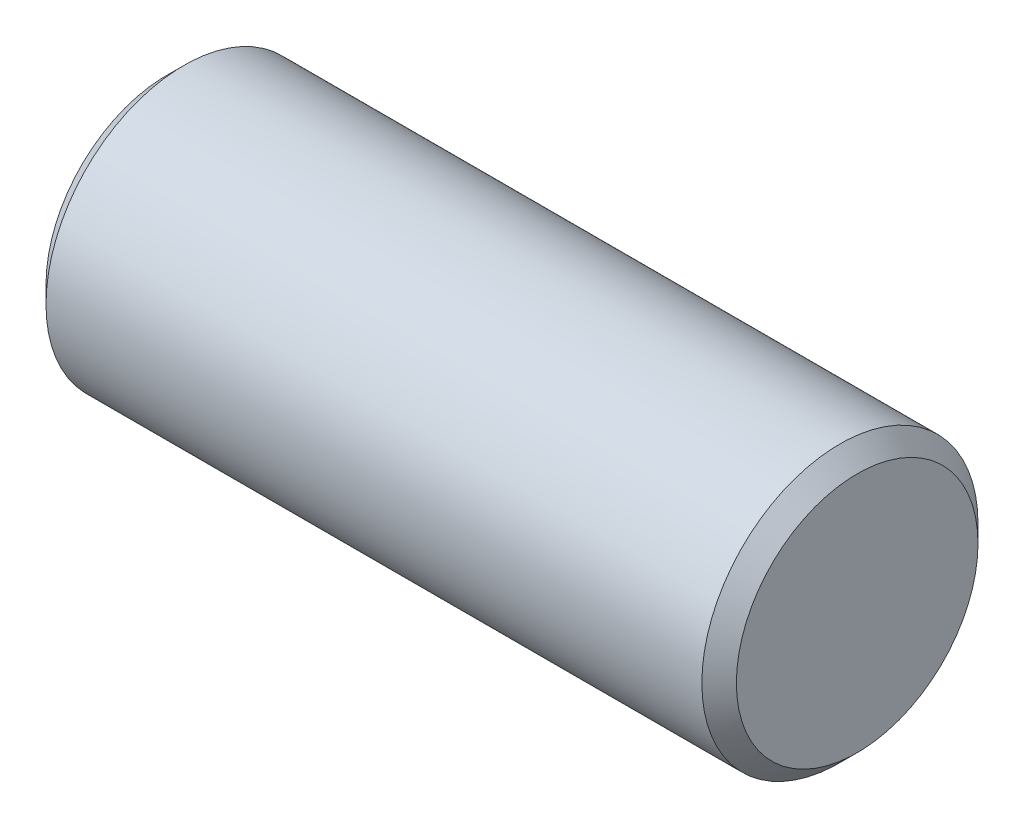
SolidWorks part; units mm, degrees
ref_plane "Front Plane" through (0, 0, 0) normal (0, 0, 1) x (1, 0, 0)
ref_plane "Top Plane" through (0, 0, 0) normal (0, 1, 0) x (1, 0, 0)
ref_plane "Right Plane" through (0, 0, 0) normal (1, 0, 0) x (0, 0, -1)
sketch "Sketch1" plane through (0, 0, 0) normal (0, 0, 1) x (1, 0, 0)
  line L0 (0, 0) -> (20, 0) construction
  line L1 (0, 0) -> (20, 0)
  line L2 (20, 0) -> (20, 4)
  line L3 (20, 4) -> (0, 4)
  line L4 (0, 4) -> (0, 0)
  dimension "L" = 20
  dimension "D" = 8
revolve "Revolve1" add sketch "Sketch1" angle 360 about L0
chamfer "Chamfer1" distance 0.5 angle 45 2 edges at (20, 0, 4) (0, 0, 4)
ref_plane "Plane1" through (0, 0, 4) normal (0, 0, 1) x (1, 0, 0)
ref_plane "Plane2" through (20, 0, 0) normal (1, 0, 0) x (0, 0, -1)
other "DeleteFace1" [suppressed]
chamfer "Chamfer2" [suppressed] distance 2 angle 45
ref_plane "Dim. KC" [suppressed] through (2, 0, 0) normal (1, 0, 0) x (0, 0, -1)
ref_plane "Plane3" [suppressed] through (2, 0, 0) normal (1, 0, 0) x (0, 0, -1)
ref_plane "Plane4" [suppressed] through (8, 0, 0) normal (1, 0, 0) x (0, 0, -1)
sketch "Sketch2" [suppressed] plane through (0, 0, 4) normal (0, 0, 1) x (1, 0, 0)
  line L0 (2, 0) -> (8, 0) construction
  line L1 (2, 1.5) -> (8, 1.5)
  line L2 (2, 1.5) -> (2, -1.5) construction
  line L3 (2, -1.5) -> (8, -1.5)
  line L4 (8, 1.5) -> (8, -1.5) construction
  line L5 (5, 1.5) -> (5, -1.5) construction
  line L6 (2, -4.4) -> (2, 4.4) construction
  line L7 (8, 1.5) -> (8, -1.5)
  line L8 (8, -4.4) -> (8, 4.4) construction
  line L9 (2, 1.5) -> (2, -1.5)
  line L12 (2, -4.4) -> (2, 4.4) construction
  dimension "A" = 6
  dimension "B_s" = 3
extrude "Boss-Extrude1" [suppressed] add sketch "Sketch2" against normal blind 1.8 separate body
fillet "Fillet1" [suppressed] type full round
fillet "Fillet2" [suppressed] type full round
sketch "Sketch3" [suppressed] plane through (0, 0, 4) normal (0, 0, 1) x (1, 0, 0)
  line L0 (9, 1.5) -> (9, -1.5) construction
  line L1 (6.5, 1.5) -> (11.5, 1.5)
  line L2 (6.5, 1.5) -> (6.5, -1.5)
  line L3 (6.5, -1.5) -> (11.5, -1.5)
  line L4 (11.5, 1.5) -> (11.5, -1.5)
  line L7 (6.5, 0) -> (11.5, 0) construction
  line L9 (10, 1.5) -> (10, -1.5) construction
  line L10 (8, 1.5) -> (8, -1.5) construction
  line L11 (2, 1.5) -> (8, 1.5) construction
  line L12 (2, -1.5) -> (8, -1.5) construction
  dimension "D1" = 1.5
  dimension "D2" = 2
  dimension "D3" = 1.5
extrude "Boss-Extrude2" [suppressed] add sketch "Sketch3" against normal blind 1.8
fillet "Fillet3" [suppressed] radius 0.1
other "DeleteFace2" [suppressed]
other "DeleteFace3" [suppressed]
combine bodies "Combine1" [suppressed] operation type subtract main body 101 bodies to subtract 146
ref_plane "KC_SEC1" [suppressed] through (5, 0, 0) normal (1, 0, 0) x (0, 0, -1)
ref_plane "KC_SEC2" [suppressed] through (9, 0, 0) normal (1, 0, 0) x (0, 0, -1)
ref_plane "Dim. WKC" [suppressed] through (2, 0, 0) normal (1, 0, 0) x (0, 0, -1)
ref_plane "Dim. K" [suppressed] through (20, 0, 0) normal (1, 0, 0) x (0, 0, -1)
ref_plane "Plane5" [suppressed] through (2, 0, 0) normal (1, 0, 0) x (0, 0, -1)
ref_plane "Plane6" [suppressed] through (20, 0, 0) normal (1, 0, 0) x (0, 0, -1)
sketch "Sketch4" [suppressed] plane through (0, 0, 4) normal (0, 0, 1) x (1, 0, 0)
  line L0 (2, 1.5) -> (2, -1.5)
  line L1 (2, 1.5) -> (8, 1.5)
  line L2 (2, 1.5) -> (2, -1.5) construction
  line L3 (2, -1.5) -> (8, -1.5)
  line L4 (8, 1.5) -> (8, -1.5)
  line L5 (2, -4.4) -> (2, 4.4) construction
  line L6 (2, -3.3) -> (2, 3.3) construction
  line L7 (8, 0) -> (2, 0) construction
  line L8 (5, 1.5) -> (5, -1.5) construction
  dimension "C" = 6
  dimension "B_s" = 3
extrude "Boss-Extrude3" [suppressed] add sketch "Sketch4" against normal blind 1.8 separate body
sketch "Sketch5" [suppressed] plane through (0, 0, 4) normal (0, 0, 1) x (1, 0, 0)
  line L0 (0, 0) -> (20, 0) construction
  line L2 (20, -3.3) -> (20, 3.3) construction
  line L4 (20, -3.3) -> (20, 3.3) construction
  line L5 (17, 1.5) -> (17, -1.5) construction
  line L9 (14, 1.5) -> (20, 1.5)
  line L10 (14, 1.5) -> (14, -1.5)
  line L11 (14, -1.5) -> (20, -1.5)
  line L12 (20, 1.5) -> (20, -1.5) construction
  line L13 (20, 1.5) -> (20, -1.5)
  dimension "B_s" = 3
  dimension "E" = 6
extrude "Boss-Extrude4" [suppressed] add sketch "Sketch5" against normal blind 1.8 separate body
sketch "Sketch6" [suppressed] plane through (0, 0, 4) normal (0, 0, 1) x (1, 0, 0)
  line L0 (2, 1.5) -> (8, 1.5) construction
  line L1 (6.5, 1.5) -> (11.5, 1.5)
  line L2 (6.5, 1.5) -> (6.5, -1.5)
  line L3 (6.5, -1.5) -> (11.5, -1.5)
  line L4 (11.5, 1.5) -> (11.5, -1.5)
  line L5 (2, -1.5) -> (8, -1.5) construction
  line L6 (8, 1.5) -> (8, -1.5) construction
  line L7 (9, 1.5) -> (9, -1.5) construction
  line L8 (10, 1.5) -> (10, -1.5) construction
  dimension "D1" = 1.5
  dimension "D2" = 2
  dimension "D3" = 1.5
extrude "Boss-Extrude5" [suppressed] add sketch "Sketch6" against normal blind 1.8
fillet "Fillet4" [suppressed] type full round
fillet "Fillet5" [suppressed] type full round
fillet "Fillet6" [suppressed] radius 0.1
fillet "Fillet7" [suppressed] type full round
fillet "Fillet8" [suppressed] type full round
fillet "Fillet9" [suppressed] radius 0.1
other "DeleteFace4" [suppressed]
other "DeleteFace5" [suppressed]
other "DeleteFace6" [suppressed]
other "DeleteFace7" [suppressed]
combine bodies "Combine2" [suppressed] operation type subtract main body 101 bodies to subtract 149 135
ref_plane "WKC_SEC1" [suppressed] through (5, 0, 0) normal (1, 0, 0) x (0, 0, -1)
ref_plane "WKC_SEC2" [suppressed] through (17, 0, 0) normal (1, 0, 0) x (0, 0, -1)
ref_plane "WKC_SEC3" [suppressed] through (9, 0, 0) normal (1, 0, 0) x (0, 0, -1)
ref_plane "Dim. KZ" [suppressed] through (2, 0, 0) normal (1, 0, 0) x (0, 0, -1)
ref_plane "Plane7" [suppressed] through (2, 0, 0) normal (1, 0, 0) x (0, 0, -1)
ref_plane "Plane8" [suppressed] through (8, 0, 0) normal (1, 0, 0) x (0, 0, -1)
sketch "Sketch7" [suppressed] plane through (0, 0, 4) normal (0, 0, 1) x (1, 0, 0)
  line L0 (0, 0) -> (8, 0) construction
  line L1 (2, 1.5) -> (8, 1.5)
  line L2 (2, 1.5) -> (2, -1.5) construction
  line L3 (2, -1.5) -> (8, -1.5)
  line L4 (8, 1.5) -> (8, -1.5) construction
  line L5 (2, -4.4) -> (2, 4.4) construction
  line L6 (2, -4.4) -> (2, 4.4) construction
  line L7 (2, 1.5) -> (2, -1.5)
  line L8 (8, 1.5) -> (8, -1.5)
  line L9 (8, -4.4) -> (8, 4.4) construction
  line L10 (5, 1.5) -> (5, -1.5) construction
  dimension "B_s" = 3
  dimension "Z" = 6
extrude "Boss-Extrude6" [suppressed] add sketch "Sketch7" against normal blind 1.8 separate body
fillet "Fillet10" [suppressed] type full round
fillet "Fillet11" [suppressed] type full round
sketch "Sketch8" [suppressed] plane through (0, 0, 4) normal (0, 0, 1) x (1, 0, 0)
  line L0 (1, 1.5) -> (1, -1.5) construction
  line L1 (-1.5, 1.5) -> (3.5, 1.5)
  line L2 (-1.5, 1.5) -> (-1.5, -1.5)
  line L3 (-1.5, -1.5) -> (3.5, -1.5)
  line L4 (3.5, 1.5) -> (3.5, -1.5)
  line L5 (2, 1.5) -> (2, -1.5) construction
  line L7 (-1.5, 0) -> (3.5, 0) construction
  line L9 (0, 1.5) -> (0, -1.5) construction
  line L10 (2, 1.5) -> (8, 1.5) construction
  line L11 (2, -1.5) -> (8, -1.5) construction
  dimension "D1" = 1.5
  dimension "D2" = 2
  dimension "D3" = 1.5
extrude "Boss-Extrude7" [suppressed] add sketch "Sketch8" against normal blind 1.8
fillet "Fillet12" [suppressed] radius 0.1
other "DeleteFace8" [suppressed]
other "DeleteFace9" [suppressed]
combine bodies "Combine3" [suppressed] operation type subtract main body 101 bodies to subtract 147
ref_plane "KZ_SEC1" [suppressed] through (5, 0, 0) normal (1, 0, 0) x (0, 0, -1)
ref_plane "KZ_SEC2" [suppressed] through (1, 0, 0) normal (1, 0, 0) x (0, 0, -1)
ref_plane "Dim. FC" [suppressed] through (1, 0, 0) normal (1, 0, 0) x (0, 0, -1)
sketch "Sketch9" [suppressed] plane through (0, 0, 0) normal (0, 1, 0) x (1, 0, 0)
  line L0 (0, 0) -> (2, 0) construction
  line L1 (1, -3) -> (2, -3)
  line L2 (1, -3) -> (1, -4)
  line L3 (1, -4) -> (2, -4)
  line L4 (2, -3) -> (2, -4)
  line L5 (1, -3.3) -> (1, 3.3) construction
  line L6 (1.5, -4) -> (1.5, -3) construction
  dimension "G" = 1
  dimension "H" = 1
  dimension "D" = 8
extrude "Cut-Extrude1" [suppressed] cut sketch "Sketch9" against normal through all and the other way through all
ref_plane "FC_SEC" [suppressed] through (1.5, 0, 0) normal (1, 0, 0) x (0, 0, -1)
ref_plane "Dim. WFC" [suppressed] through (1, 0, 0) normal (1, 0, 0) x (0, 0, -1)
ref_plane "Dim. W" [suppressed] through (19, 0, 0) normal (1, 0, 0) x (0, 0, -1)
sketch "Sketch10" [suppressed] plane through (0, 0, 0) normal (0, 1, 0) x (1, 0, 0)
  line L0 (0, 0) -> (19, 0) construction
  line L1 (1, -4) -> (2, -4)
  line L2 (1, -4) -> (1, -3)
  line L3 (1, -3) -> (2, -3)
  line L4 (2, -4) -> (2, -3)
  line L5 (1.5, -3) -> (1.5, -4) construction
  line L6 (19, -4) -> (18, -4)
  line L7 (19, -4) -> (19, -3)
  line L8 (19, -3) -> (18, -3)
  line L9 (18, -4) -> (18, -3)
  line L10 (1, -3.3) -> (1, 3.3) construction
  line L11 (19, -3.3) -> (19, 3.3) construction
  line L12 (18.5, -3) -> (18.5, -4) construction
  dimension "J" = 1
  dimension "V" = 1
  dimension "H" = 1
  dimension "D" = 8
  dimension "H_s_R" = 1
extrude "Cut-Extrude2" [suppressed] cut sketch "Sketch10" against normal through all and the other way through all
ref_plane "WFC_SEC1" [suppressed] through (1.5, 0, 0) normal (1, 0, 0) x (0, 0, -1)
ref_plane "WFC_SEC2" [suppressed] through (18.5, 0, 0) normal (1, 0, 0) x (0, 0, -1)
ref_plane "Dim. SFC" [suppressed] through (1, 0, 0) normal (1, 0, 0) x (0, 0, -1)
sketch "Sketch11" [suppressed] plane through (0, 0, 0) normal (0, 1, 0) x (1, 0, 0)
  line L0 (0, 0) -> (2, 0) construction
  line L1 (1, -4) -> (2, -4)
  line L2 (1, -4) -> (1, -3)
  line L3 (1, -3) -> (2, -3)
  line L4 (2, -4) -> (2, -3)
  line L5 (1, -3.3) -> (1, 3.3) construction
  line L6 (1.5, -3) -> (1.5, -4) construction
  dimension "SG" = 1
  dimension "H" = 1
  dimension "D" = 8
extrude "Cut-Extrude3" [suppressed] cut sketch "Sketch11" against normal through all and the other way through all
pattern_circular "CirPattern1" [suppressed] count 2 every 120 of bodies 119
ref_plane "Plane9" [suppressed] through (0, 0, 0) normal (0, -0.5, 0.866) x (1, 0, 0)
sketch "Sketch12" [suppressed] plane through (0, 0, 0) normal (0, -0.5, 0.866) x (1, 0, 0)
  line L0 (0, 0) -> (2, 0) construction
  line L2 (1, -3) -> (2, -3)
  line L3 (1, -3) -> (1, -4)
  line L4 (1, -4) -> (2, -4)
  line L5 (2, -3) -> (2, -4)
  line L6 (1, -3.3) -> (1, 3.3) construction
  dimension "D" = 8
  dimension "SG" = 1
  dimension "H" = 1
ref_plane "SFC_SEC" [suppressed] through (1.5, 0, 0) normal (1, 0, 0) x (0, 0, -1)
sketch "Sketch13" [suppressed] plane through (1.5, 0, 0) normal (1, 0, 0) x (0, 0, -1)
  line L0 (-4, 0) -> (-3, 0) construction
  line L1 (-3, 0) -> (-4, 0) construction
  line L2 (2, -3.4641) -> (1.5, -2.5981) construction
  line L3 (1.5, -2.5981) -> (2, -3.4641) construction
  line L4 (1.5, -2.5981) -> (2, -3.4641) construction
  dimension "ANG" = 120
sketch "Sketch14" [suppressed] plane through (0, 0, 0) normal (0, 1, 0) x (1, 0, 0)
  line L0 (0, 0) -> (20, 0) construction
  line L1 (1.5, 4) -> (1.5, 3.5) construction
  line L2 (0, 3.5) -> (3, 3.5)
  line L3 (0, 3.5) -> (0, 4)
  line L4 (0, 4) -> (3, 4)
  line L5 (3, 3.5) -> (3, 4)
  line L6 (17, 3.5) -> (20, 3.5)
  line L7 (17, 3.5) -> (17, 4)
  line L8 (17, 4) -> (20, 4)
  line L9 (20, 3.5) -> (20, 4)
  line L10 (0, -4) -> (3, -4)
  line L11 (0, -4) -> (0, -3.5)
  line L12 (0, -3.5) -> (3, -3.5)
  line L13 (3, -4) -> (3, -3.5)
  line L14 (17, -4) -> (20, -4)
  line L15 (17, -4) -> (17, -3.5)
  line L16 (17, -3.5) -> (20, -3.5)
  line L17 (20, -4) -> (20, -3.5)
  line L18 (1.5, -3.5) -> (1.5, -4) construction
  line L19 (18.5, 4) -> (18.5, 3.5) construction
  line L20 (18.5, -3.5) -> (18.5, -4) construction
  dimension "D" = 8
  dimension "W_1" = 7
  dimension "KWC" = 3
  dimension "KWC_L1" = 3
  dimension "KWC_R1" = 3
  dimension "KWC_R2" = 3
  dimension "W_1_R" = 7
extrude "Cut-Extrude4" [suppressed] cut sketch "Sketch14" against normal through all and the other way through all
ref_plane "KWC_SEC1" [suppressed] through (1.5, 0, 0) normal (1, 0, 0) x (0, 0, -1)
ref_plane "KWC_SEC2" [suppressed] through (18.5, 0, 0) normal (1, 0, 0) x (0, 0, -1)
sketch "Sketch15" [suppressed] plane through (0, 0, 0) normal (0, 1, 0) x (1, 0, 0)
  line L0 (0, 0) -> (20, 0) construction
  line L1 (1.5, -3) -> (1.5, -4) construction
  line L2 (0, 3) -> (3, 3)
  line L3 (0, 3) -> (0, 4)
  line L4 (0, 4) -> (3, 4)
  line L5 (3, 3) -> (3, 4)
  line L6 (17, 3) -> (20, 3)
  line L7 (17, 3) -> (17, 4)
  line L8 (17, 4) -> (20, 4)
  line L9 (20, 3) -> (20, 4)
  line L10 (0, -4) -> (3, -4)
  line L11 (0, -4) -> (0, -3)
  line L12 (0, -3) -> (3, -3)
  line L13 (3, -4) -> (3, -3)
  line L14 (17, -4) -> (20, -4)
  line L15 (17, -4) -> (17, -3)
  line L16 (17, -3) -> (20, -3)
  line L17 (20, -4) -> (20, -3)
  line L18 (18.5, -3) -> (18.5, -4) construction
  dimension "D" = 8
  dimension "KWC_L1" = 3
  dimension "KWC_R1" = 3
  dimension "WC" = 6
  dimension "KWC" = 3
  dimension "KWC_R2" = 3
  dimension "WC_R" = 6
extrude "Cut-Extrude5" [suppressed] cut sketch "Sketch15" against normal through all and the other way through all
ref_plane "WC_SEC1" [suppressed] through (1.5, 0, 0) normal (1, 0, 0) x (0, 0, -1)
ref_plane "WC_SEC2" [suppressed] through (18.5, 0, 0) normal (1, 0, 0) x (0, 0, -1)
sketch "Sketch16" [suppressed] plane through (0, 0, 0) normal (0, 0, 1) x (1, 0, 0)
  line L0 (20, 4) -> (0, 4) construction
  line L1 (1.1, 3.5) -> (2, 3.5)
  line L2 (1.1, 3.5) -> (1.1, 4)
  line L3 (1.1, 4) -> (2, 4)
  line L4 (2, 3.5) -> (2, 4)
  line L5 (0, 0) -> (2, 0) construction
  line L6 (0, 4) -> (0, 0) construction
  dimension "D_s_1" = 7
  dimension "M_s" = 0.9
  dimension "TA" = 2
revolve "Cut-Revolve1" [suppressed] cut sketch "Sketch16" angle 360 about L5
sketch "Sketch17" [suppressed] plane through (0, 0, 0) normal (0, 0, 1) x (1, 0, 0)
  line L1 (18, 3.5) -> (18.9, 3.5)
  line L2 (18, 3.5) -> (18, 4)
  line L3 (18, 4) -> (18.9, 4)
  line L4 (18.9, 3.5) -> (18.9, 4)
  line L5 (0, 0) -> (20, 0) construction
  line L7 (20, -3.3) -> (20, 3.3) construction
  dimension "D_s_1" = 7
  dimension "M_s" = 0.9
  dimension "D" = 8
  dimension "TB" = 2
revolve "Cut-Revolve2" [suppressed] cut sketch "Sketch17" angle 360 about L5
sketch "Sketch18" [suppressed] plane through (0, 0, 0) normal (0, 0, 1) x (1, 0, 0)
  line L0 (0, 0) -> (20, 0) construction
  line L1 (0, 4) -> (0, -4) construction
  line L3 (1, 4) -> (5, 4)
  line L4 (1, 4) -> (1, 3.5)
  line L5 (1, 3.5) -> (5, 3.5)
  line L6 (5, 4) -> (5, 3.5)
  line L7 (20, 4) -> (0, 4) construction
  line L8 (20, -3.3) -> (20, 3.3) construction
  dimension "D_s_2" = 7
  dimension "UC" = 1
  dimension "L1_s" = 4
revolve "Cut-Revolve3" [suppressed] cut sketch "Sketch18" angle 360 about L0
ref_plane "Dim. SC" [suppressed] through (2, 0, 0) normal (1, 0, 0) x (0, 0, -1)
sketch "Sketch19" [suppressed] plane through (0, 0, 0) normal (0, 1, 0) x (1, 0, 0)
  line L0 (20, -3.3) -> (20, 3.3) construction
  line L1 (2, -3.5) -> (10, -3.5)
  line L2 (2, -3.5) -> (2, -4)
  line L3 (2, -4) -> (10, -4)
  line L4 (10, -3.5) -> (10, -4)
  line L5 (2, 4) -> (10, 4)
  line L6 (2, 4) -> (2, 3.5)
  line L7 (2, 3.5) -> (10, 3.5)
  line L8 (10, 4) -> (10, 3.5)
  line L9 (6, 4) -> (6, 3.5) construction
  line L10 (6, -3.5) -> (6, -4) construction
  line L12 (0, 0) -> (20, 0) construction
  line L14 (2, -3.3) -> (2, 3.3) construction
  dimension "W_2" = 7
  dimension "L2_s" = 8
  dimension "D" = 8
  dimension "L2_s_L1" = 8
extrude "Cut-Extrude6" [suppressed] cut sketch "Sketch19" against normal through all and the other way through all
ref_plane "SC_SEC" [suppressed] through (6, 0, 0) normal (1, 0, 0) x (0, 0, -1)
equation "\"Plane dim\"= \"D@Sketch1\" * 0.5"
equation "\"D1@Plane3\"= if ( \"KC@Dim. KC\" < 1 , 0 , \"KC@Dim. KC\" )"
equation "\"D1@Plane4\" = if ( \"KC@Dim. KC\" > \"L@Sketch1\" - \"A@Sketch2\" - 1 , \"L@Sketch1\" , \"KC@Dim. KC\" + \"A@Sketch2\" )"
equation "\"D1@Plane5\"=if ( \"WKC@Dim. WKC\" < 1 , 0 , \"WKC@Dim. WKC\" )"
equation "\"D1@Plane6\"=if ( \"K@Dim. K\" < 1 , 0 , \"K@Dim. K\" )"
equation "\"D1@Plane7\"=if ( \"KZ@Dim. KZ\" < 1 , 0 , \"KZ@Dim. KZ\" )"
equation "\"D1@Plane8\"=if ( \"KZ@Dim. KZ\" > \"L@Sketch1\" - \"Z@Sketch7\" - 1 , \"L@Sketch1\", \"KZ@Dim. KZ\" + \"Z@Sketch7\" )"
equation "\"D1@Sketch3\"=\"B_s@Sketch2\"/2"
equation "\"D3@Sketch3\"=\"B_s@Sketch2\"/2"
equation "\"D1@Sketch8\"=\"B_s@Sketch7\"/2"
equation "\"D3@Sketch8\"=\"B_s@Sketch7\"/2"
equation "\"D1@Sketch6\"=\"B_s@Sketch4\"/2"
equation "\"D3@Sketch6\"=\"B_s@Sketch4\"/2"
equation "\"D@Sketch12\" = \"D@Sketch11\""
equation "\"SG@Sketch12\" = \"SG@Sketch11\""
equation "\"H@Sketch12\"= \"H@Sketch11\""
